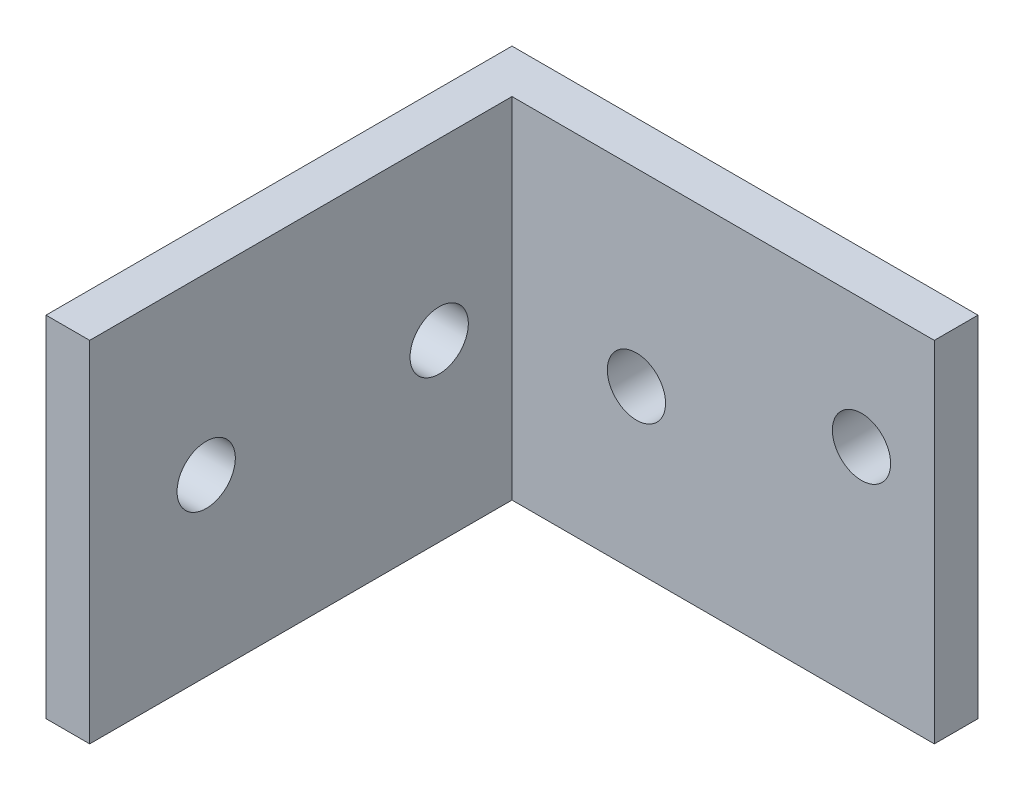
SolidWorks part; units mm, degrees
material "6061 Alloy"
ref_plane "Front Plane" through (0, 0, 0) normal (0, 0, 1) x (1, 0, 0)
ref_plane "Top Plane" through (0, 0, 0) normal (0, 1, 0) x (1, 0, 0)
ref_plane "Right Plane" through (0, 0, 0) normal (1, 0, 0) x (0, 0, -1)
sketch "Sketch1" plane through (0, 0, 0) normal (0, 1, 0) x (1, 0, 0)
  line L0 (0, 0) -> (0, 46.0375)
  line L1 (0, 46.0375) -> (46.0375, 46.0375)
  line L2 (46.0375, 46.0375) -> (46.0375, 50.8)
  line L3 (46.0375, 50.8) -> (-4.7625, 50.8)
  line L4 (-4.7625, 50.8) -> (-4.7625, 0)
  line L5 (-4.7625, 0) -> (0, 0)
  dimension "D1" = 50.8
  dimension "D2" = 50.8
  dimension "D3" = 4.7625
  dimension "D4" = 4.7625
extrude "Boss-Extrude1" add sketch "Sketch1" along normal blind 38.1
sketch "Sketch2" plane through (0, 0, -50.8) normal (0, 0, -1) x (-1, 0, 0)
  line L2 (-46.0375, 26.2053) -> (4.7625, 12.5935) construction
  line L3 (-46.0375, 38.1) -> (-46.0375, 0) construction
  line L4 (4.7625, 38.1) -> (4.7625, 0) construction
  line L5 (-46.0375, 38.1) -> (4.7625, 38.1) construction
  circle A0 centre (-38.1, 24.0784) radius 3.175
  circle A1 centre (-13.5655, 17.5044) radius 3.175
  dimension "D1" = 6.35
  dimension "D2" = 15
  dimension "D3" = 0
  dimension "D4" = 25.4
  dimension "D7" = 6.35
  dimension "D5" = 0
  dimension "D6" = 7.9375
extrude "Cut-Extrude1" cut sketch "Sketch2" against normal blind 38.1
sketch "Sketch3" plane through (-4.7625, 0, 0) normal (-1, 0, 0) x (0, 0, 1)
  line L2 (-50.8, 0) -> (0, 0) construction
  line L3 (0, 38.1) -> (0, 0) construction
  circle A0 centre (-12.7, 19.05) radius 3.175
  circle A1 centre (-38.1, 19.05) radius 3.175
  dimension "D1" = 6.35
  dimension "D2" = 6.35
  dimension "D3" = 19.05
  dimension "D4" = 19.05
  dimension "D5" = 12.7
  dimension "D6" = 25.4
extrude "Cut-Extrude3" cut sketch "Sketch3" against normal up to next
